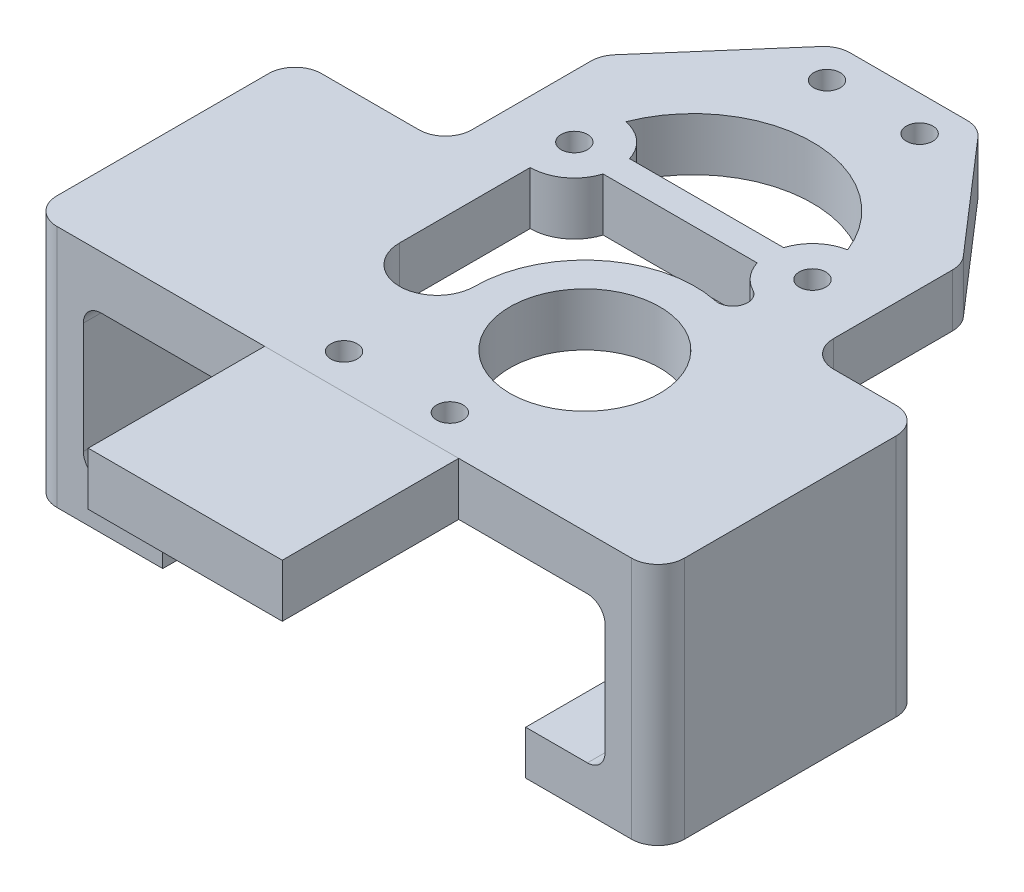
SolidWorks part; units mm, degrees
material "PLA"
ref_plane "Front Plane" through (0, 0, 0) normal (0, 0, 1) x (1, 0, 0)
ref_plane "Top Plane" through (0, 0, 0) normal (0, 1, 0) x (1, 0, 0)
ref_plane "Right Plane" through (0, 0, 0) normal (1, 0, 0) x (0, 0, -1)
sketch "Sketch1" plane through (0, 0, 0) normal (0, 1, 0) x (1, 0, 0)
  line L0 (-11, 0) -> (11, 0)
  line L1 (0, 0) -> (0, 62) construction
  line L2 (-8, 62) -> (8, 62)
  line L3 (11, 0) -> (20.4896, 17.6053)
  line L4 (20.4896, 17.6053) -> (20.4896, 47.6053)
  line L5 (20.4896, 47.6053) -> (8, 62)
  line L6 (-11, 0) -> (-20.5104, 17.6233)
  line L7 (-20.5104, 17.6233) -> (-20.5104, 47.6233)
  line L8 (-20.5104, 47.6233) -> (-8, 62)
  line L9 (20.4896, 17.6053) -> (10.3666, 23.0618) construction
  line L10 (-5.25, 57.9999) -> (5.25, 57.9999) construction
  line L11 (-13.5, 37.6053) -> (13.5, 37.6053) construction
  line L12 (-8.7303, 39.1053) -> (8.7303, 39.1053)
  line L13 (-8.7303, 36.1053) -> (8.7303, 36.1053)
  line L14 (-13.5, 32.6053) -> (-13.5, 17.7879)
  line L15 (11, 0) -> (33.5896, 0)
  line L16 (33.5896, 0) -> (33.5896, 30)
  line L17 (33.5896, 30) -> (20.4896, 30)
  line L18 (27.5896, 30) -> (27.5896, 0)
  line L19 (-11, 0) -> (-31.5502, 0)
  line L20 (-11, 0) -> (11, 0)
  line L21 (-11, 0) -> (-11, -20)
  line L22 (-11, -20) -> (11, -20)
  line L23 (11, 0) -> (11, -20)
  line L24 (-31.5502, 0) -> (-31.5502, 30)
  line L25 (-31.5502, 30) -> (-20.5104, 30)
  line L26 (25.5197, 17.7565) -> (27.5896, 17.7565) construction
  line L27 (25.5242, 21.1573) -> (25.5152, 14.3557) construction
  line L28 (-29.4803, 17.8291) -> (-31.5502, 17.8291) construction
  line L29 (-29.4758, 21.2299) -> (-29.4848, 14.4283) construction
  line L31 (-31.5502, 30) -> (-37.5502, 30)
  line L32 (-31.5502, 30) -> (-31.5502, 0)
  line L33 (-31.5502, 0) -> (-37.5502, 0)
  line L34 (-37.5502, 30) -> (-37.5502, 0)
  circle A0 centre (7.5197, 17.7803) radius 8.5
  circle A1 centre (6, 4) radius 1.5
  circle A2 centre (-6, 4) radius 1.5
  circle A3 centre (-5.25, 57.9999) radius 1.5
  circle A4 centre (5.25, 57.9999) radius 1.5
  circle A5 centre (-13.5, 37.6053) radius 1.5
  circle A6 centre (13.5, 37.6053) radius 1.5
  arc A7 (-8.7303, 39.1053) -> (-12.5741, 42.5188) centre (-13.5, 37.6053) ccw
  arc A8 (10.0627, 30.0188) -> (-4.9803, 17.786) centre (7.5197, 17.7803) ccw
  arc A9 (8.7303, 36.1053) -> (11.188, 33.172) centre (13.5, 37.6053) ccw
  arc A10 (12.5741, 42.5188) -> (-12.5741, 42.5188) centre (0, 37.6053) ccw
  arc A11 (-13.5, 32.6053) -> (-8.7303, 36.1053) centre (-13.5, 37.6053) ccw
  arc A12 (-13.5, 17.7879) -> (-4.9803, 17.786) centre (-9.2402, 17.7879) ccw
  arc A13 (10.0627, 30.0188) -> (11.188, 33.172) centre (10.4065, 31.6735) ccw
  arc A14 (12.5741, 42.5188) -> (8.7303, 39.1053) centre (13.5, 37.6053) ccw
  point P7 (0, 62)
  point P17 (20.4896, 17.6053)
  point P24 (0, 57.9999)
  point P27 (0, 37.6053)
  dimension "D7" = 17
  dimension "D13" = 3
  dimension "D14" = 3
  dimension "D19" = 3
  dimension "D20" = 10
  dimension "D23" = 1.69
  dimension "D24" = 13.5
  dimension "D25" = 5
  dimension "D1" = 22
  dimension "D2" = 16
  dimension "D3" = 62
  dimension "D4" = 20
  dimension "D5" = 30
  dimension "D6" = 41
  dimension "D8" = 11.5
  dimension "D9" = 11.5
  dimension "D10" = 6
  dimension "D11" = 4
  dimension "D12" = 12
  dimension "D15" = 10.5
  dimension "D17" = 10
  dimension "D18" = 27
  dimension "D21" = 4
  dimension "D26" = 14.8174
  dimension "D16" = 22
  dimension "D27" = 3
  dimension "D28" = 6
  dimension "D29" = 7.1
  dimension "D30" = 30
  dimension "D31" = 20
  dimension "D32" = 6
  dimension "D22" = 45
extrude "Boss-Extrude1" add sketch "Sketch1" along normal blind 6 contours L8 L7 L6 L0 L3 L4 L5 L2 A13 A8 A12 L14 A11 L13 A9 A6 A5 A4 A3 A0 A1 A2 A10 A14 L12 A7 | L18 L17 L4 L3 L15 | L17 L18 L15 L16 | L23 L0 L21 L22 | L25 L24 L19 L6 L7 | L31 L34 L33 L24 region at (-15.1011, 0, -9.1647) region at (-24.2755, 0, -13.1572) region at (0, 0, 10) region at (22.1485, 0, -12.4276) region at (-34.5502, 0, -15) region at (30.5896, 0, -15)
extrude "Ressalto-extrusão1" add sketch "Sketch1<5>" against normal blind 21.6 contours L17 L18 L15 L16 region at (30.5896, 0, -15)
sketch "Sketch1<5>" plane through (0, 0, 0) normal (0, 1, 0) x (1, 0, 0) same geometry as "Sketch1"
sketch "Esboço1" plane through (27.5896, 0, 0) normal (-1, 0, 0) x (0, 0, 1)
  line L0 (0, -21.6) -> (0, 0) construction
  line L1 (-30, -21.6) -> (0, -21.6)
  line L2 (-30, -21.6) -> (-30, -16.6)
  line L3 (-30, -16.6) -> (0, -16.6)
  line L4 (0, -21.6) -> (0, -16.6)
  dimension "D1" = 5
extrude "Ressalto-extrusão2" add sketch "Esboço1" along normal blind 9
sketch "Esboço2" plane through (0, -21.6, 0) normal (0, -1, 0) x (1, 0, 0)
  line L0 (18.5896, -30) -> (18.5896, 0) construction
  line L1 (20.5896, -10.4) -> (25.5896, -10.4)
  line L2 (20.5896, -10.4) -> (20.5896, -25.4)
  line L3 (20.5896, -25.4) -> (25.5896, -25.4)
  line L4 (25.5896, -10.4) -> (25.5896, -25.4)
  line L5 (33.5896, -30) -> (18.5896, -30) construction
  dimension "D1" = 7
  dimension "D2" = 5
  dimension "D3" = 15
  dimension "D4" = 4.6
extrude "Corte-extrusão1" cut sketch "Esboço2" against normal up to next
fillet "Filete2" radius 2 4 edges at (25.5896, -19.1, -25.4) (20.5896, -19.1, -25.4) (25.5896, -19.1, -10.4) (20.5896, -19.1, -10.4)
ref_plane "Plano1" through (-1.9803, 0, 0) normal (-1, 0, 0) x (0, 0, 1)
mirror "Espelhar1" about plane through (-1.9803, 0, 0) normal (-1, 0, 0) of "Filete2", "Ressalto-extrusão1", "Ressalto-extrusão2", "Corte-extrusão1"
fillet "Fillet1" radius 3 10 edges at (8, 3, -62) (20.4896, 3, -47.6053) (-8, 3, -62) (-20.5104, 3, -47.6233) (20.4896, 3, -30) (33.5896, -7.8, 0) (33.5896, -7.8, -30) (-37.5502, -7.8, -30) (-37.5502, -7.8, 0) (-20.5104, 3, -30)
fillet "Filete1" radius 2 4 edges at (27.5896, -16.6, -15) (27.5896, 0, -15) (-31.5502, -16.6, -15) (-31.5502, 0, -15)
sketch "Esboço3" plane through (0, 0, 20) normal (0, 0, 1) x (1, 0, 0)
  line L0 (-10.75, 0.25) -> (10.75, 0.25)
  line L1 (10.75, 0.25) -> (10.75, 5.75)
  line L2 (10.75, 5.75) -> (-10.75, 5.75)
  line L3 (-10.75, 5.75) -> (-10.75, 0.25)
  line L4 (-11, 0) -> (11, 0)
  line L5 (11, 0) -> (11, 6)
  line L6 (11, 6) -> (-11, 6)
  line L7 (-11, 6) -> (-11, 0)
  line L8 (-11, 0) -> (11, 0)
  line L9 (11, 0) -> (11, 6)
  line L10 (11, 6) -> (-11, 6)
  line L11 (-11, 6) -> (-11, 0)
  line L12 (-10.75, 5.75) -> (-10.75, 6)
  line L13 (10.75, 5.75) -> (10.75, 6)
  line M9 (-11, 0) -> (11, 0)
  line M10 (11, 0) -> (11, 6)
  line M11 (11, 6) -> (-11, 6)
  line M12 (-11, 6) -> (-11, 0)
  dimension "D1" = 0
  dimension "D2" = 0.25
extrude "Para impressão" [suppressed] cut sketch "Esboço3" against normal up to surface (20 mm away) contours L13 L1 L0 L3 L12 L10 M12 M9 M10 M11
sketch "Esboço4" plane through (0, -21.6, 0) normal (0, -1, 0) x (1, 0, 0)
  line L0 (-1.9803, 13.2) -> (-1.9803, -13.2) construction
  line L1 (-26.5502, -15.9) -> (22.5896, -15.9)
  line L2 (-26.5502, -15.9) -> (-26.5502, -19.9)
  line L3 (-26.5502, -19.9) -> (22.5896, -19.9)
  line L4 (22.5896, -15.9) -> (22.5896, -19.9)
  line L5 (-26.5502, -15.9) -> (22.5896, -19.9) construction
  line L6 (-26.5502, -19.9) -> (22.5896, -15.9) construction
  line L7 (-29.5502, -17.9) -> (-26.5502, -17.9) construction
  line L8 (-29.5502, -23.4) -> (-29.5502, -12.4) construction
  line L9 (-24.5502, -12.4) -> (-24.5502, -23.4) construction
  point P0 (-1.9803, -17.9)
  line M9 (-22.5502, -30) -> (-22.5502, 0)
  line M16 (-24.5502, -12.4) -> (-24.5502, -23.4)
  dimension "D1" = 4
  dimension "D2" = 2
extrude "Corte-extrusão3" cut sketch "Esboço4" against normal blind 1.5 contours L3 L1 M16 M9 | L4 L1 L3 M9 region at (-23.5502, -21.6, -17.9) region at (0.0197, -21.6, -17.9)
fillet "Filete3" radius 0.3 4 edges at (19.5896, -20.1, -19.9) (19.5896, -20.1, -15.9) (-23.5502, -20.1, -15.9) (-23.5502, -20.1, -19.9)
sketch "Esboço5" plane through (0, 6, 0) normal (0, 1, 0) x (1, 0, 0)
  line L1 (-11, 0) -> (11, 0)
  line L2 (-11, 0) -> (-11, -20)
  line L3 (-11, -20) -> (11, -20)
  line L4 (11, 0) -> (11, -20)
split line "Linha de divisão1"
equation "\"D32@Sketch1\"=\"D28@Sketch1\""
